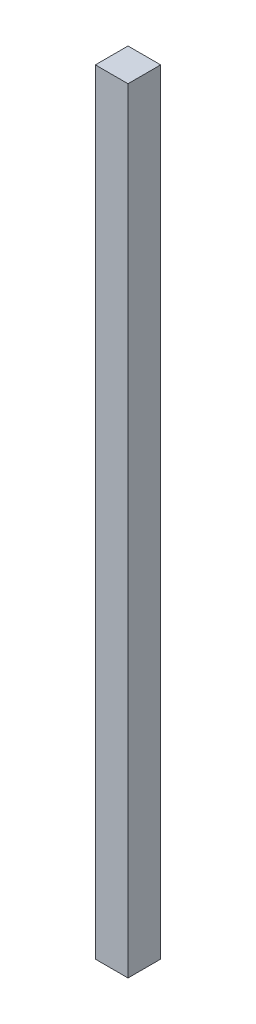
SolidWorks part; units mm, degrees
material "Oak"
ref_plane "Front Plane" through (0, 0, 0) normal (0, 0, 1) x (1, 0, 0)
ref_plane "Top Plane" through (0, 0, 0) normal (0, 1, 0) x (1, 0, 0)
ref_plane "Right Plane" through (0, 0, 0) normal (1, 0, 0) x (0, 0, -1)
sketch "Sketch1" plane through (0, 0, 0) normal (0, 1, 0) x (1, 0, 0)
  line L1 (-44.45, -44.45) -> (44.45, -44.45)
  line L2 (-44.45, -44.45) -> (-44.45, 44.45)
  line L3 (-44.45, 44.45) -> (44.45, 44.45)
  line L4 (44.45, -44.45) -> (44.45, 44.45)
  line L5 (-44.45, -44.45) -> (44.45, 44.45) construction
  line L6 (-44.45, 44.45) -> (44.45, -44.45) construction
  point P0 (0, 0)
  dimension "D1" = 88.9
extrude "Boss-Extrude2" add sketch "Sketch1" along normal blind 2108.2
